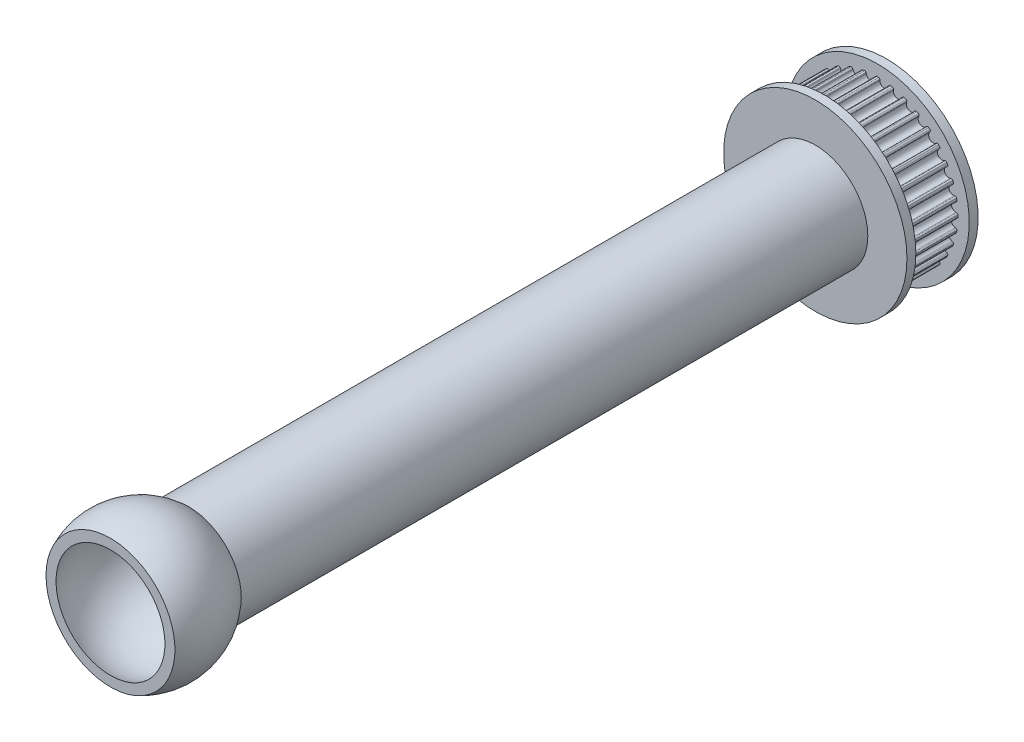
SolidWorks part; units mm, degrees
ref_plane "前视基准面" through (0, 0, 0) normal (0, 0, 1) x (1, 0, 0)
ref_plane "上视基准面" through (0, 0, 0) normal (0, 1, 0) x (1, 0, 0)
ref_plane "右视基准面" through (0, 0, 0) normal (1, 0, 0) x (0, 0, -1)
sketch "Sketch2" plane through (0, 0, 0) normal (0, 0, 1) x (1, 0, 0)
  circle A0 centre (0, 0) radius 45.15
  dimension "D1" = 90.3
extrude "Extrude1" add sketch "Sketch2" along normal blind 30
sketch "Sketch1" plane through (0, 0, 0) normal (0, 0, 1) x (1, 0, 0)
  line L0 (0, 0) -> (0, 45.835) construction
  line L1 (0, 0) -> (-3.9948, 45.6606) construction
  line L2 (-1.2656, 44.3946) -> (-1.2821, 43.9222)
  line L3 (-6.4627, 43.9399) -> (-6.3644, 43.4775)
  circle A0 centre (0, 0) radius 45.835 construction
  arc A1 (-0.4946, 45.1473) -> (-7.3526, 44.5473) centre (0, 0) ccw
  arc A2 (-6.3644, 43.4775) -> (-1.2821, 43.9222) centre (-3.8505, 44.0119) ccw
  arc A3 (-0.4946, 45.1473) -> (-1.2656, 44.3946) centre (-0.4861, 44.3673) ccw
  arc A4 (-7.3526, 44.5473) -> (-6.4627, 43.9399) centre (-7.2256, 43.7777) cw
  point P4 (45.6606, 3.9948)
  point P5 (44.2732, 11.863)
  point P6 (41.5406, 19.3707)
  point P7 (37.5458, 26.2899)
  point P8 (32.4102, 32.4102)
  point P9 (26.2899, 37.5458)
  point P10 (19.3707, 41.5406)
  point P11 (11.863, 44.2732)
  point P12 (3.9948, 45.6606)
  point P13 (-3.9948, 45.6606)
  point P14 (-11.863, 44.2732)
  point P15 (-19.3707, 41.5406)
  point P16 (-26.2899, 37.5458)
  point P17 (-32.4102, 32.4102)
  point P18 (-37.5458, 26.2899)
  point P19 (-41.5406, 19.3707)
  point P20 (-44.2732, 11.863)
  point P21 (-45.6606, 3.9948)
  point P22 (-45.6606, -3.9948)
  point P23 (-44.2732, -11.863)
  point P24 (-41.5406, -19.3707)
  point P25 (-37.5458, -26.2899)
  point P26 (-32.4102, -32.4102)
  point P27 (-26.2899, -37.5458)
  point P28 (-19.3707, -41.5406)
  point P29 (-11.863, -44.2732)
  point P30 (-3.9948, -45.6606)
  point P31 (3.9948, -45.6606)
  point P32 (11.863, -44.2732)
  point P33 (19.3707, -41.5406)
  point P34 (26.2899, -37.5458)
  point P35 (32.4102, -32.4102)
  point P36 (37.5458, -26.2899)
  point P37 (41.5406, -19.3707)
  point P38 (44.2732, -11.863)
  point P39 (45.6606, -3.9948)
  dimension "D1" = 91.67
  dimension "D2" = 90.3
  dimension "D3" = 5.14
  dimension "D4" = 3.54
  dimension "D5" = 1.56
  dimension "D6" = 7
extrude "Extrude2" cut sketch "Sketch1" along normal up to surface (30 mm away) up to face at (45.15, 0, 30)
pattern_circular "CirPattern1" count 36 over 360 about axis through (0, 0, 30) along (0, 0, 1) of "Extrude2"
sketch "Sketch6" plane through (0, 0, 30) normal (0, 0, 1) x (1, 0, 0)
  circle A0 centre (0, 0) radius 29.5
  dimension "D1" = 59
extrude "Extrude6" add sketch "Sketch6" along normal blind 344
sketch "Sketch7" plane through (0, 0, 30) normal (0, 0, 1) x (1, 0, 0)
  circle A0 centre (0, 0) radius 29.5 construction
  circle A1 centre (0, 0) radius 29.5
  circle A2 centre (0, 0) radius 51.5
  dimension "D1" = 103
extrude "Extrude7" add sketch "Sketch7" along normal blind 5
sketch "Sketch8" plane through (0, 0, 0) normal (0, 0, -1) x (-1, 0, 0)
  circle A0 centre (0, 0) radius 51.5
  dimension "D1" = 103
extrude "Extrude8" add sketch "Sketch8" along normal blind 5
sketch "Sketch9" plane through (0, 0, 0) normal (0, 1, 0) x (1, 0, 0)
  line L0 (-29.5, -374) -> (29.5, -374) construction
  line L1 (-40, -414) -> (40, -414)
  arc A0 (40, -414) -> (-40, -414) centre (0, -414) ccw
  point P2 (0, -414)
  dimension "D1" = 80
revolve "Revolve1" add sketch "Sketch9" angle 360 about L1
sketch "Sketch10" plane through (0, 0, 374) normal (0, 0, 1) x (1, 0, 0)
  circle A1 centre (0, 0) radius 29.5
  circle A2 centre (0, 0) radius 29.5
  dimension "D1" = 0
extrude "Extrude9" add sketch "Sketch10" along normal up to next
sketch "Sketch11" plane through (0, 0, 0) normal (0, 1, 0) x (1, 0, 0)
  line L0 (0, -414) -> (0, -386.9861) construction
  line L1 (29.5, -386.9861) -> (-29.5, -386.9861) construction
  line L2 (-36.2077, -431) -> (36.2077, -431)
  arc A0 (-36.2077, -431) -> (36.2077, -431) centre (0, -414) ccw
  arc A1 (-29.5, -386.9861) -> (29.5, -386.9861) centre (0, -414) ccw construction
  dimension "D1" = 40
  dimension "D2" = 17
extrude "Extrude10" cut sketch "Sketch11" against normal through all both and the other way through all
sketch "Sketch12" plane through (0, 0, 0) normal (0, 1, 0) x (1, 0, 0)
  line L0 (0, -449) -> (0, -379)
  arc A0 (0, -449) -> (0, -379) centre (0, -414) ccw
  arc A1 (36.2077, -431) -> (29.5, -386.9861) centre (0, -414) ccw construction
  dimension "D1" = 70
revolve "Cut-Revolve1" cut sketch "Sketch12" angle 360 about L0
equation "\"全局配合间隙\"= 2mm"
equation "\"安装轴_直径\"= 67mm"
equation "\"安装孔_直径\"= 69mm"
equation "\"一级驱动短轴_外径\"= 83mm"
equation "\"一级驱动短轴_外内径差\"= 10mm"
equation "\"一级驱动长轴_外径\"= \"一级驱动短轴_外径\" - \"一级驱动短轴_外内径差\" - \"全局配合间隙\""
equation "\"一级驱动长轴_外内径差\"= 10mm"
equation "\"二级驱动等速轴_直径\"= \"一级驱动长轴_外径\" - \"一级驱动长轴_外内径差\" - \"全局配合间隙\""
equation "\"D1@Sketch6\"=\"二级驱动等速轴_直径\""
